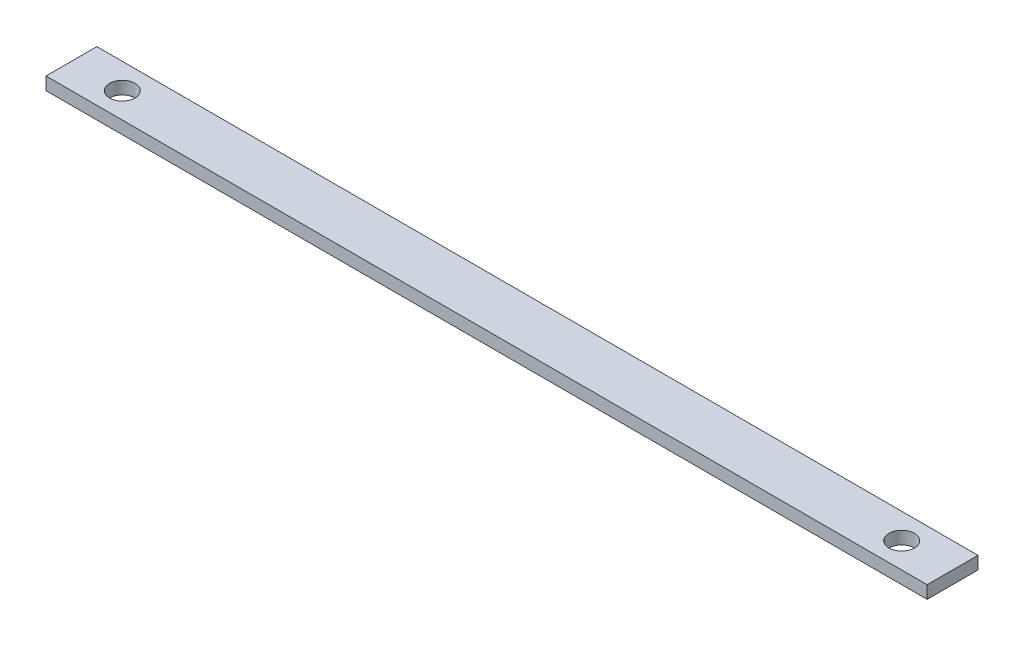
SolidWorks part; units mm, degrees
ref_plane "Front Plane" through (0, 0, 0) normal (0, 0, 1) x (1, 0, 0)
ref_plane "Top Plane" through (0, 0, 0) normal (0, 1, 0) x (1, 0, 0)
ref_plane "Right Plane" through (0, 0, 0) normal (1, 0, 0) x (0, 0, -1)
sketch "Sketch1" plane through (0, 0, 0) normal (0, 1, 0) x (1, 0, 0)
  line L1 (0, 0) -> (219.964, 0)
  line L2 (0, 0) -> (0, 12.7)
  line L3 (0, 12.7) -> (219.964, 12.7)
  line L4 (219.964, 0) -> (219.964, 12.7)
  dimension "D1" = 219.964
  dimension "D2" = 12.7
extrude "Boss-Extrude1" add sketch "Sketch1" along normal blind 3.175
sketch "Sketch2" plane through (0, 3.175, 0) normal (0, 1, 0) x (1, 0, 0)
  line L0 (0, 12.7) -> (0, 0) construction
  line L1 (219.964, 0) -> (219.964, 12.7) construction
  circle A0 centre (12.7, 6.35) radius 3.175
  circle A1 centre (207.264, 6.35) radius 3.175
  point P8 (0, 6.35)
  dimension "D1" = 6.35
  dimension "D2" = 12.7
  dimension "D3" = 12.7
  dimension "D4" = 6.35
extrude "Cut-Extrude1" cut sketch "Sketch2" against normal through all
